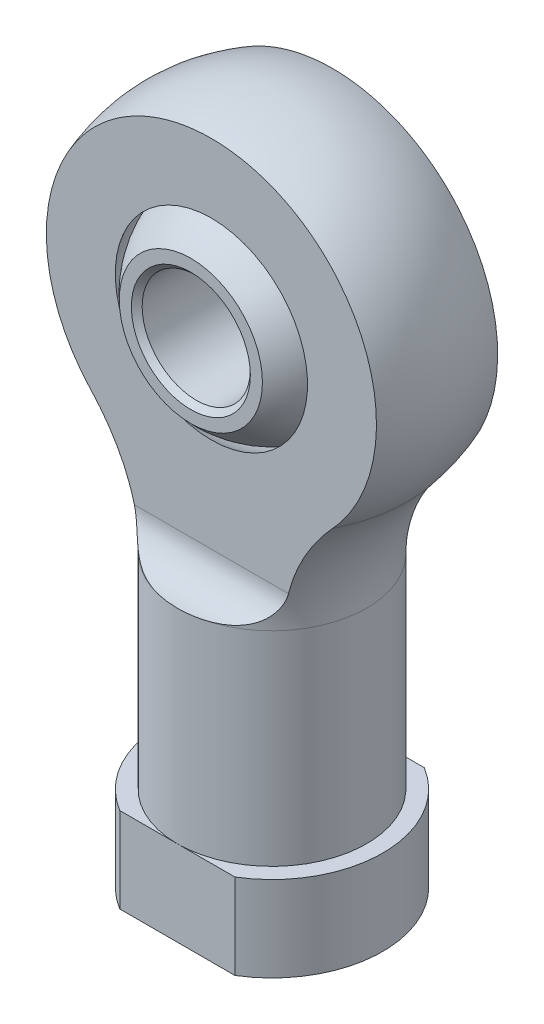
SolidWorks part; units mm, degrees
ref_plane "Front" through (0, 0, 0) normal (0, 0, 1) x (1, 0, 0)
ref_plane "Top" through (0, 0, 0) normal (0, 1, 0) x (1, 0, 0)
ref_plane "Right" through (0, 0, 0) normal (1, 0, 0) x (0, 0, -1)
sketch "Sketch1" plane through (0, 0, 0) normal (0, 0, 1) x (1, 0, 0)
  line L0 (0, 0) -> (0, -14.2875) construction
  line L1 (0, -14.2875) -> (3.175, -14.2875) construction
  line L2 (3.175, -14.2875) -> (3.175, 0) construction
  line L3 (3.175, 0) -> (0, 0) construction
  line L5 (0, 26.1937) -> (0, 0) construction
  line L6 (0, 26.1937) -> (10.3187, 26.1937) construction
  line L7 (10.3187, 26.1937) -> (10.3187, 15.875) construction
  line L8 (-3.175, -14.2875) -> (-3.175, 0) construction
  line L9 (5.5563, 2.6882) -> (5.5563, -9.2837)
  line L10 (5.5563, -9.2837) -> (6.5024, -9.2837)
  line L11 (6.5024, -9.2837) -> (6.5024, -14.2875)
  line L12 (6.5024, -14.2875) -> (0, -14.2875)
  line L13 (0, -14.2875) -> (0, 2.6882)
  line L14 (0, 2.6882) -> (5.5563, 2.6882)
  line L15 (0, 5.5563) -> (5.9628, 5.5563) construction
  arc A0 (7.9375, 9.2816) -> (0, 26.1937) centre (0, 15.875) ccw construction
  circle A1 centre (0, 15.875) radius 3.175 construction
  circle A2 centre (0, 15.875) radius 6.35 construction
  circle A3 centre (0, 15.875) radius 6.6675 construction
  arc A4 (7.9375, 9.2816) -> (0, 5.5563) centre (0, 15.875) cw construction
  arc A5 (7.9375, 9.2816) -> (5.5563, 2.6882) centre (15.875, 2.6882) ccw construction
  dimension "A" = 6.35
  dimension "Ball Dia" = 12.7
  dimension "B" = 20.6375
  dimension "D1" = 13.335
  dimension "D" = 30.1625
  dimension "E" = 14.2875
  dimension "Wrench Flats" = 11.1125
  dimension "Base Dia" = 13.0048
  dimension "Base Height" = 5.0038
  dimension "Thread Dia" = 6.35
revolve "Revolve1" add sketch "Sketch1" angle 360 about L5
sketch "Sketch12" plane through (0, 0, 0) normal (0, 0, 1) x (1, 0, 0)
  line L1 (0, 0) -> (0, 2.6882) construction
  line L2 (6.5024, -14.2875) -> (0, -14.2875) construction
  line L3 (3.175, -14.2875) -> (3.175, 0) construction
  line L4 (3.175, 0) -> (0, 0) construction
  line L5 (3.175, -14.2875) -> (0, -14.2875)
  line L6 (3.175, -14.2875) -> (3.175, 0)
  line L7 (3.175, 0) -> (0, 0)
  line L8 (0, -14.2875) -> (0, 2.6882) construction
  line L9 (0, -14.2875) -> (0, 0)
revolve "Revolve4" add sketch "Sketch12" angle 360 about L1
sketch "Sketch15" plane through (0, -14.2875, 0) normal (0, -1, 0) x (1, 0, 0)
  circle A0 centre (0, 0) radius 3.175 construction
  circle A1 centre (0, 0) radius 3.175
curve "Helix/Spiral1" pitch 1.4111 height 15.6986 turns 11.125 parameters "pitch"=1.4111
sketch "Sketch16" plane through (0, 0, 0) normal (0, 0, 1) x (1, 0, 0)
  line L0 (3.175, -14.2875) -> (2.2585, -14.8167)
  line L1 (2.2585, -14.8167) -> (2.2585, -14.9931)
  line L2 (2.2585, -14.9931) -> (3.175, -15.5222)
  line L3 (3.175, -15.5222) -> (3.175, -14.2875)
  line L4 (2.2585, -14.9049) -> (3.175, -14.9049) construction
  line L5 (2.7167, -14.5521) -> (2.7167, -15.2576) construction
  dimension "D2" = 60
  dimension "D3" = 0.7056
sweep "Cut-Sweep1" cut profiles "Sketch16" path "Helix/Spiral1" align with end faces yes
sketch "Sketch14" plane through (0, -9.2837, 0) normal (0, 1, 0) x (-1, 0, 0)
  line L0 (-5.5563, 0) -> (5.5563, 0) construction
  line L1 (5.5563, 5.5563) -> (-5.5563, 5.5563)
  line L2 (5.5563, 5.5563) -> (5.5563, -5.5563) construction
  line L3 (5.5563, -5.5563) -> (-5.5563, -5.5563)
  line L4 (-5.5563, 5.5563) -> (-5.5563, -5.5563) construction
  line L5 (-5.5563, -5.5563) -> (-5.5563, -6.5024)
  line L6 (-5.5563, -6.5024) -> (5.5563, -6.5024)
  line L7 (5.5563, -6.5024) -> (5.5563, -5.5563)
  line L8 (5.5563, 5.5563) -> (5.5563, 6.5024)
  line L9 (5.5563, 6.5024) -> (-5.5563, 6.5024)
  line L10 (-5.5563, 6.5024) -> (-5.5563, 5.5563)
  circle A0 centre (0, 0) radius 6.5024 construction
extrude "Cut-Extrude5" cut sketch "Sketch14" against normal through all and the other way through all
sketch "Sketch2" plane through (0, 0, 0) normal (0, 0, 1) x (1, 0, 0)
  line L0 (3.175, 0) -> (-3.175, 0) construction
  line L1 (-3.175, 0) -> (-3.175, -1.0583) construction
  line L2 (-3.175, -1.0583) -> (3.175, 0) construction
  line L3 (3.175, 0) -> (3.1967, -0.1305) construction
  line L4 (3.1967, -0.1305) -> (3.349, -1.0439)
  line L5 (3.349, -1.0439) -> (2.7296, -0.8119)
  line L6 (2.7296, -0.8119) -> (2.6861, -0.5509)
  line L7 (2.6861, -0.5509) -> (3.1967, -0.1305)
  line L8 (2.7078, -0.6814) -> (3.2729, -0.5872) construction
  line L9 (-3.175, -14.2875) -> (-3.175, 0) construction
  line L10 (3.175, 0) -> (3.175, -0.6035) construction
  line L11 (3.175, -0.6035) -> (-3.175, -1.6619) construction
  line L12 (-3.175, -1.6619) -> (-3.175, -1.0583) construction
  line L13 (3.175, -14.2875) -> (3.175, 0) construction
  line L14 (-0.1888, 0) -> (0.1888, -2.2654) construction
  line L15 (0, 0) -> (0, -1.1327) construction
  line L16 (3.175, 0) -> (0, 0) construction
  line L17 (-3.1967, -0.1305) -> (-3.349, -1.0439) construction
  line L18 (-2.6861, -0.5509) -> (-3.1967, -0.1305) construction
  line L19 (-2.7296, -0.8119) -> (-2.6861, -0.5509) construction
  line L20 (-3.349, -1.0439) -> (-2.7296, -0.8119) construction
  line L21 (0.1888, 0) -> (-0.1888, -2.2654) construction
  point P19 (0, -1.1327)
  dimension "D1" = 0.1323
  dimension "D2" = 0.2646
  dimension "Thread Pitch" = 1.0583
  dimension "D4" = 1.0583
  dimension "D3" = 60
combine bodies "Combine1" operation type subtract main body 123 bodies to subtract 124
sketch "Sketch17" plane through (0, -14.2875, 0) normal (0, -1, 0) x (1, 0, 0)
  circle A1 centre (0, 0) radius 3.175
  circle A2 centre (0, 0) radius 3.175
  dimension "D1" = 0
extrude "Extrude1" cut sketch "Sketch17" against normal through all draft 45
sketch "Sketch4" plane through (0, 0, 0) normal (0, 0, 1) x (1, 0, 0)
  line L0 (0, 9.2075) -> (0, 2.6882)
  line L3 (5.5563, 2.6882) -> (0, 2.6882)
  line L4 (0, 26.1937) -> (0, 0) construction
  line L5 (0, 26.1938) -> (0, 22.5425)
  line L6 (0, 26.1938) -> (0, 28.7338) construction
  arc A0 (7.9375, 9.2816) -> (0, 26.1938) centre (0, 15.875) ccw construction
  arc A1 (7.9375, 9.2816) -> (0, 26.1938) centre (0, 15.875) ccw
  arc A2 (7.9375, 9.2816) -> (5.5563, 2.6882) centre (15.875, 2.6882) ccw construction
  arc A3 (7.9375, 9.2816) -> (5.5563, 2.6882) centre (15.875, 2.6882) ccw
  circle A4 centre (0, 15.875) radius 6.6675 construction
  arc A5 (0, 9.2075) -> (0, 22.5425) centre (0, 15.875) ccw
  dimension "D1" = 2.54
revolve "Revolve2" add sketch "Sketch4" angle 360 about L6
sketch "Sketch5" plane through (0, 0, 0) normal (1, 0, 0) x (0, 0, -1)
  line L0 (3.556, 26.1937) -> (10.3187, 26.1937)
  line L1 (-3.556, 26.1937) -> (3.556, 26.1937) construction
  line L2 (-3.556, 26.1937) -> (-3.556, 2.6882)
  line L3 (-3.556, 2.6882) -> (3.556, 2.6882) construction
  line L4 (3.556, 26.1937) -> (3.556, 2.6882)
  line L5 (10.3187, 26.1937) -> (10.3188, 2.6882)
  line L6 (10.3188, 2.6882) -> (3.556, 2.6882)
  line L7 (-3.556, 2.6882) -> (-10.3188, 2.6882)
  line L8 (-10.3188, 2.6882) -> (-10.3187, 26.1937)
  line L9 (-10.3187, 26.1937) -> (-3.556, 26.1937)
  line L11 (-5.5563, 2.6882) -> (-5.5563, -9.2837) construction
  arc A0 (7.9375, 9.2816) -> (-7.9375, 9.2816) centre (0, 15.875) ccw construction
  dimension "D1" = 2.0003
  dimension "F" = 7.112
extrude "Cut-Extrude1" cut sketch "Sketch5" against normal through all and the other way through all
fillet "Fillet1" radius 2.0003 2 edges at (0, 2.6882, 3.556) (0, 2.6882, -3.556)
sketch "Sketch7" plane through (0, 0, 0) normal (0, 0, 1) x (1, 0, 0)
  line L0 (0, 22.225) -> (0, 9.525)
  line L1 (0, 26.1937) -> (0, 0) construction
  line L2 (0, 0) -> (0, 9.525) construction
  arc A0 (0, 9.525) -> (0, 22.225) centre (0, 15.875) ccw
  circle A1 centre (0, 15.875) radius 6.35 construction
revolve "Revolve3" add sketch "Sketch7" angle 360 about L2
sketch "Sketch8" plane through (0, 0, 0) normal (1, 0, 0) x (0, 0, -1)
  line L0 (-3.556, 26.1937) -> (3.556, 26.1937) construction
  line L1 (-4.7625, 26.1937) -> (4.7625, 26.1937) construction
  line L2 (-4.7625, 26.1937) -> (-4.7625, 2.6882)
  line L3 (-4.7625, 2.6882) -> (4.7625, 2.6882) construction
  line L4 (4.7625, 26.1937) -> (4.7625, 2.6882)
  line L5 (4.7625, 26.1937) -> (10.3187, 26.1937)
  line L6 (10.3187, 26.1937) -> (10.3188, 2.6882)
  line L7 (10.3188, 2.6882) -> (4.7625, 2.6882)
  line L8 (-4.7625, 2.6882) -> (-10.3188, 2.6882)
  line L9 (-10.3188, 2.6882) -> (-10.3187, 26.1937)
  line L10 (-10.3187, 26.1937) -> (-4.7625, 26.1937)
  dimension "C" = 9.525
extrude "Cut-Extrude3" cut sketch "Sketch8" against normal through all and the other way through all
sketch "Sketch10" plane through (0, 0, 0) normal (0, 0, 1) x (1, 0, 0)
  circle A0 centre (0, 15.875) radius 3.175 construction
  circle A1 centre (0, 15.875) radius 3.175
extrude "Cut-Extrude4" cut sketch "Sketch10" against normal through all and the other way through all
chamfer "Chamfer1" distance 0.3175 angle 45 2 edges at (0, 12.7, -4.7625) (0, 19.05, 4.7625)
sketch "Sketch11" plane through (0, 0, 0) normal (1, 0, 0) x (0, 0, -1)
  line L0 (0, 15.875) -> (-4.7625, 17.4224) construction
  line L2 (0, 15.875) -> (-4.7625, 14.3276) construction
  line L3 (0, 26.1937) -> (0, 0) construction
  line L4 (-4.7625, 26.1937) -> (-4.7625, 2.6882) construction
  line L5 (0, 15.875) -> (0.0074, 15.875) construction
  dimension "Swivel" = 36
sketch "Sketch18" plane through (0, 0, 0) normal (1, 0, 0) x (0, 0, -1)
  line L1 (-3.175, 0) -> (3.175, 0)
  line L2 (-3.175, 0) -> (-3.175, -14.2875)
  line L3 (-3.175, -14.2875) -> (3.175, -14.2875)
  line L4 (3.175, 0) -> (3.175, -14.2875)
  dimension "D1" = 6.35
sketch "Sketch19" plane through (0, 0, 0) normal (0, 0, 1) x (1, 0, 0)
  line L1 (-3.175, 0) -> (3.175, 0)
  line L2 (-3.175, 0) -> (-3.175, -14.2875)
  line L3 (-3.175, -14.2875) -> (3.175, -14.2875)
  line L4 (3.175, 0) -> (3.175, -14.2875)
  dimension "D1" = 6.35
equation "\"D1@Sketch2\"=\"Thread Pitch@Sketch2\"/8"
equation "\"D2@Sketch2\"=\"Thread Pitch@Sketch2\"/4"
equation "\"D4@Sketch2\"=\"Thread Pitch@Sketch2\""
equation "\"D1@Sketch1\"=\"Ball Dia@Sketch1\"*1.05"
equation "\"D1@Chamfer1\"=\"A@Sketch1\"/20"
equation "\"D1@Fillet1\"=\"D1@Sketch5\""
equation "\"D1@Sketch16\" = \"pitch@Helix/Spiral1\"*.125"
equation "\"D3@Sketch16\" = \"pitch@Helix/Spiral1\"*.5"
equation "\"D3@Helix/Spiral1\" = \"E@Sketch1\"+\"pitch@Helix/Spiral1\""
equation "\"D1@Sketch18\" = \"Thread Dia@Sketch1\""
equation "\"D1@Sketch19\" = \"Thread Dia@Sketch1\""
